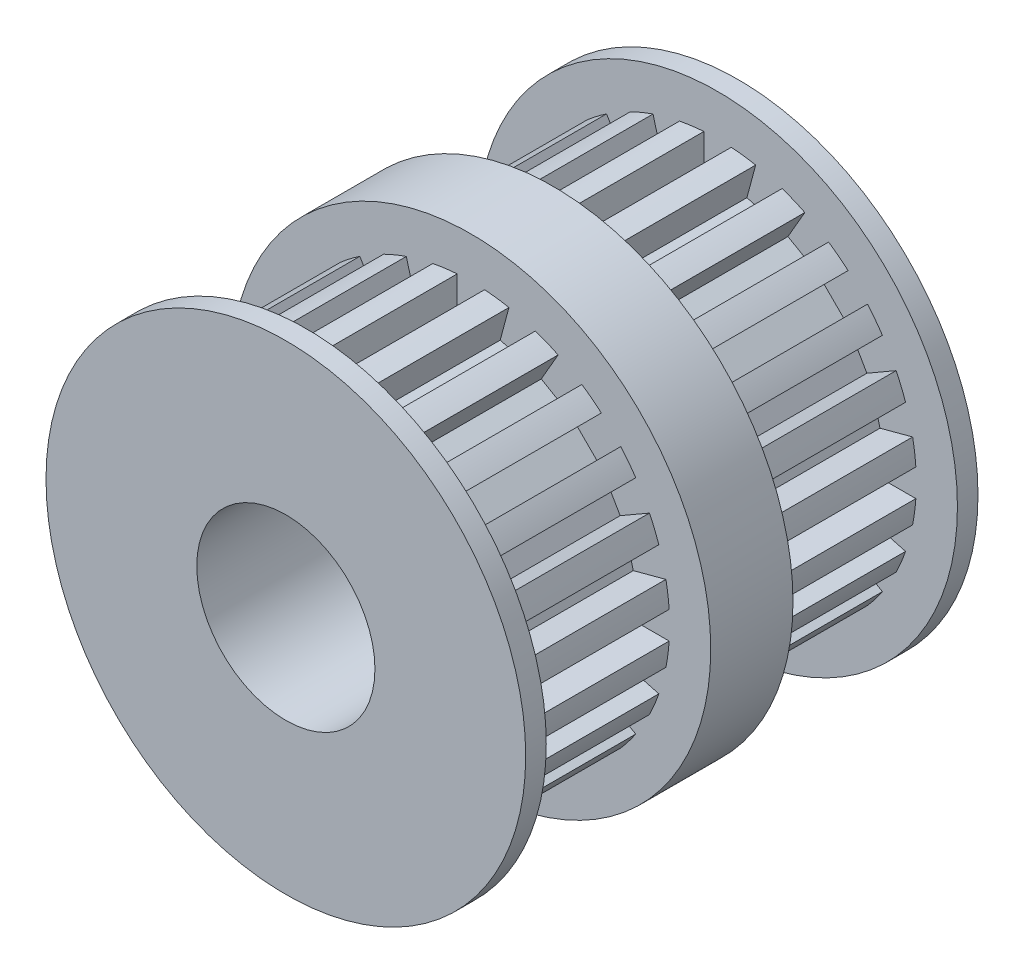
SolidWorks part; units mm, degrees
ref_plane "Front Plane" through (0, 0, 0) normal (0, 0, 1) x (1, 0, 0)
ref_plane "Top Plane" through (0, 0, 0) normal (0, 1, 0) x (1, 0, 0)
ref_plane "Right Plane" through (0, 0, 0) normal (1, 0, 0) x (0, 0, -1)
sketch "Sketch1" plane through (0, 0, 0) normal (0, 0, 1) x (1, 0, 0)
  circle A0 centre (0, 0) radius 8.89
  dimension "D1" = 17.78
extrude "Boss-Extrude1" add sketch "Sketch1" against normal blind 0.762
sketch "Sketch2" plane through (0, 0, -0.762) normal (0, 0, -1) x (-1, 0, 0)
  circle A0 centre (0, 0) radius 7.366
  dimension "D1" = 14.732
extrude "Boss-Extrude2" add sketch "Sketch2" along normal blind 6.096
sketch "Sketch3" plane through (0, 0, -6.858) normal (0, 0, -1) x (-1, 0, 0)
  circle A0 centre (0, 0) radius 8.89
  dimension "D1" = 17.78
extrude "Boss-Extrude3" add sketch "Sketch3" along normal blind 5.334
sketch "Sketch4" plane through (0, 0, 0) normal (0, 0, 1) x (1, 0, 0)
  circle A0 centre (0, 0) radius 3.302
  dimension "D1" = 6.604
extrude "Cut-Extrude1" cut sketch "Sketch4" against normal blind 57.912
ref_plane "Plane2" through (-7.366, 0, 0) normal (-1, 0, 0) x (0, 0, 1)
sketch "Sketch5" plane through (-7.366, 0, 0) normal (-1, 0, 0) x (0, 0, 1)
  line L0 (-6.858, -7.366) -> (-6.858, 7.366) construction
  line L1 (-6.858, 0.508) -> (-0.762, 0.508)
  line L2 (-6.858, 0.508) -> (-6.858, -0.508)
  line L3 (-6.858, -0.508) -> (-0.762, -0.508)
  line L4 (-0.762, 0.508) -> (-0.762, -0.508)
  line L5 (-0.762, 7.366) -> (-0.762, -7.366) construction
  point P8 (-6.858, 0)
  dimension "D1" = 1.016
extrude "Cut-Extrude2" cut sketch "Sketch5" against normal blind 1.27
ref_axis "Axis1" through (0, 0, -12.192) along (0, 0, 1)
pattern_circular "CirPattern1" count 24 over 360 about axis through (0, 0, -12.192) along (0, 0, 1) of "Cut-Extrude2"
sketch "Sketch6" plane through (0, 0, 0) normal (0, 1, 0) x (1, 0, 0)
  line L0 (-8.89, 12.192) -> (-8.89, 6.858) construction
  line L1 (8.89, 12.192) -> (-8.89, 12.192)
  line L2 (8.89, 12.192) -> (8.89, 8.382)
  line L3 (8.89, 8.382) -> (-8.89, 8.382)
  line L4 (-8.89, 12.192) -> (-8.89, 8.382)
  dimension "D1" = 3.81
extrude "Cut-Extrude3" cut sketch "Sketch6" against normal blind 152.4 and the other way blind 152.4
ref_plane "Plane3" through (0, 0, -8.382) normal (0, 0, -1) x (-1, 0, 0)
sketch "Sketch7" plane through (0, 0, -8.382) normal (0, 0, -1) x (-1, 0, 0)
  circle A0 centre (0, 0) radius 8.89
  dimension "D1" = 17.78
extrude "Boss-Extrude4" add sketch "Sketch7" along normal blind 1.524
mirror "Mirror7" about plane through (0, 0, -8.382) normal (0, 0, -1) of "Boss-Extrude2"
mirror "Mirror8" about plane through (0, 0, -8.382) normal (0, 0, -1) of "CirPattern1"
mirror "Mirror9" about plane through (0, 0, -8.382) normal (0, 0, -1) of "Boss-Extrude1"
sketch "Sketch8" plane through (0, 0, -16.764) normal (0, 0, -1) x (-1, 0, 0)
  circle A0 centre (0, 0) radius 3.302
  dimension "D1" = 6.604
extrude "Cut-Extrude4" cut sketch "Sketch8" against normal blind 22.098
